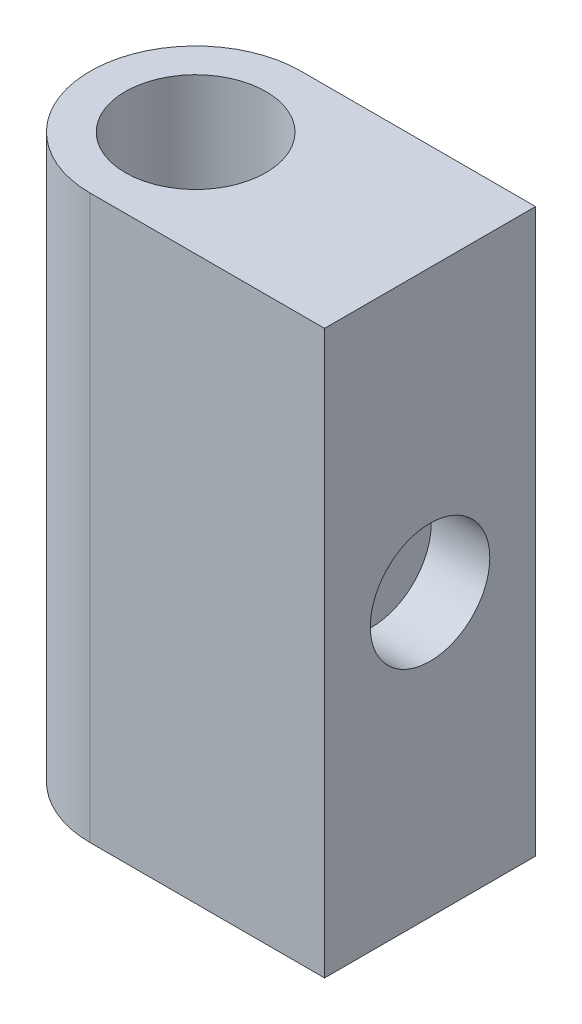
SolidWorks part; units mm, degrees
ref_plane "Front Plane" through (0, 0, 0) normal (0, 0, 1) x (1, 0, 0)
ref_plane "Top Plane" through (0, 0, 0) normal (0, 1, 0) x (1, 0, 0)
ref_plane "Right Plane" through (0, 0, 0) normal (1, 0, 0) x (0, 0, -1)
sketch "Sketch1" plane through (0, 0, 0) normal (0, 1, 0) x (1, 0, 0)
  line L0 (0, 0) -> (0, 5.8529)
  line L1 (0, 4.5) -> (10, 4.5)
  line L2 (0, 4.5) -> (0, -4.5)
  line L3 (0, -4.5) -> (10, -4.5)
  line L4 (10, 4.5) -> (10, -4.5)
  circle A0 centre (0, 0) radius 3
  circle A1 centre (0, 0) radius 4.5
  dimension "D1" = 6
  dimension "D2" = 9
  dimension "D3" = 4.5
  dimension "D4" = 4.5
  dimension "D5" = 0
  dimension "D6" = 10
extrude "Boss-Extrude1" add sketch "Sketch1" along normal blind 24 contours L2 A1 A0 | L2 A1 A0 | A1 L3 L4 L1 region at (-3.1006, 0, 0) region at (0.1006, 0, -3.75) region at (6.6891, 0, 0)
sketch "Sketch2" plane through (10, 0, 0) normal (1, 0, 0) x (0, 0, -1)
  line L0 (0, 24) -> (0, 0)
  line L1 (4.5, 24) -> (-4.5, 24) construction
  circle A0 centre (0, 12) radius 2.55
  dimension "D1" = 5.1
extrude "Cut-Extrude1" cut sketch "Sketch2" against normal blind 2.5 contours L0 A0 | L0 A0 region at (10, 12, -1.0823) region at (10, 12, 1.0823)
sketch "Sketch3" plane through (7.5, 0, 0) normal (1, 0, 0) x (0, 0, -1)
  circle A0 centre (1.987, 10.3927) radius 0.0057
  circle A1 centre (0, 12) radius 2.55 construction
  circle A2 centre (0, 12) radius 2.55
  circle A3 centre (0, 12) radius 1
  dimension "D1" = 2
extrude "Cut-Extrude3" cut sketch "Sketch3" against normal blind 8.5 contours A3 region at (7.5, 12, 0)
ref_plane "Plane1" through (0.5, 0, 0) normal (1, 0, 0) x (0, 0, -1)
sketch "Sketch4" plane through (0.5, 0, 0) normal (1, 0, 0) x (0, 0, -1)
  circle A1 centre (0, 12) radius 2.55
  circle A2 centre (0, 12) radius 2.55
  dimension "D1" = 0
extrude "Cut-Extrude4" cut sketch "Sketch4" along normal offset from surface (5 mm away) 2 up to face at (7.5, 12, -1)
